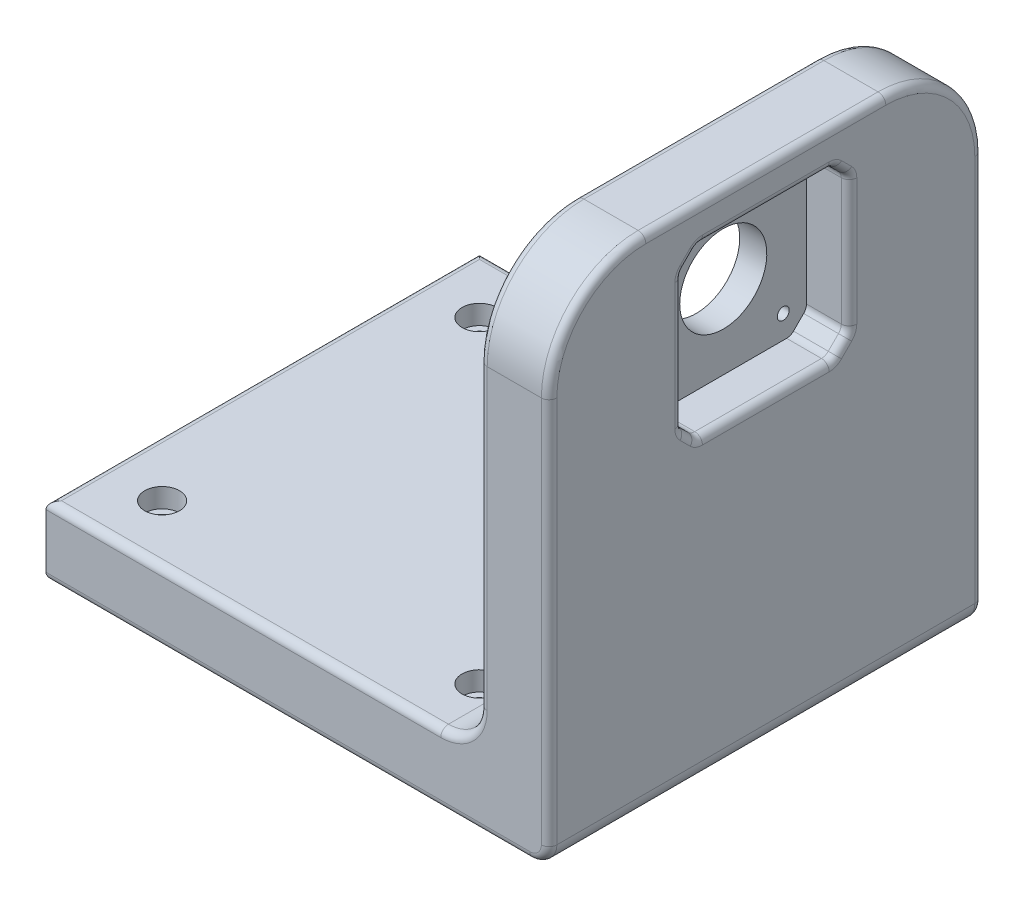
SolidWorks part; units mm, degrees
note: The reader was unsure of these and kept them because the rebuilt part matched: shared geometry of "Sketch9<3>".
ref_plane "Front" through (0, 0, 0) normal (0, 0, 1) x (1, 0, 0)
ref_plane "Top" through (0, 0, 0) normal (0, 1, 0) x (1, 0, 0)
ref_plane "Right" through (0, 0, 0) normal (1, 0, 0) x (0, 0, -1)
sketch "Sketch1" plane through (0, 0, 0) normal (0, 0, 1) x (1, 0, 0)
  line L1 (130, 0) -> (130, 130)
  line L2 (130, 130) -> (112, 130)
  line L3 (112, 130) -> (112, 18)
  line L8 (0, 0) -> (0, 18)
  line L9 (0, 0) -> (130, 0)
  line L10 (112, 18) -> (0, 18)
  point P4 (0, 0)
  dimension "D1" = 112
  dimension "D2" = 18
  dimension "D3" = 18
  dimension "D4" = 112
extrude "Boss-Extrude1" add sketch "Sketch1" along normal mid plane 112
sketch "Sketch2" plane through (130, 0, 0) normal (1, 0, 0) x (0, 0, -1)
  line L0 (-16.3716, 77.65) -> (16.3716, 77.65)
  line L1 (18.1393, 78.3822) -> (20.7678, 81.0107)
  line L2 (21.5, 82.7784) -> (21.5, 115.5216)
  line L3 (20.7678, 117.2893) -> (18.1393, 119.9178)
  line L4 (16.3716, 120.65) -> (-16.3716, 120.65)
  line L5 (-18.1393, 119.9178) -> (-20.7678, 117.2893)
  line L6 (-21.5, 115.5216) -> (-21.5, 82.7784)
  line L7 (-20.7678, 81.0107) -> (-18.1393, 78.3822)
  line L8 (-16.3716, 78.65) -> (16.3716, 78.65)
  line L9 (17.4322, 79.0893) -> (20.0607, 81.7178)
  line L10 (20.5, 82.7784) -> (20.5, 115.5216)
  line L11 (20.0607, 116.5822) -> (17.4322, 119.2107)
  line L12 (16.3716, 119.65) -> (-16.3716, 119.65)
  line L13 (-17.4322, 119.2107) -> (-20.0607, 116.5822)
  line L14 (-20.5, 115.5216) -> (-20.5, 82.7784)
  line L15 (-20.0607, 81.7178) -> (-17.4322, 79.0893)
  line L16 (-16.3716, 78.65) -> (16.3716, 78.65) construction
  line L17 (17.4322, 79.0893) -> (20.0607, 81.7178) construction
  line L18 (20.5, 82.7784) -> (20.5, 115.5216) construction
  line L19 (20.0607, 116.5822) -> (17.4322, 119.2107) construction
  line L20 (16.3716, 119.65) -> (-16.3716, 119.65) construction
  line L21 (-17.4322, 119.2107) -> (-20.0607, 116.5822) construction
  line L22 (-20.5, 115.5216) -> (-20.5, 82.7784) construction
  line L23 (-20.0607, 81.7178) -> (-17.4322, 79.0893) construction
  arc A0 (16.3716, 77.65) -> (18.1393, 78.3822) centre (16.3716, 80.15) ccw
  arc A1 (20.7678, 81.0107) -> (21.5, 82.7784) centre (19, 82.7784) ccw
  arc A2 (21.5, 115.5216) -> (20.7678, 117.2893) centre (19, 115.5216) ccw
  arc A3 (18.1393, 119.9178) -> (16.3716, 120.65) centre (16.3716, 118.15) ccw
  arc A4 (-16.3716, 120.65) -> (-18.1393, 119.9178) centre (-16.3716, 118.15) ccw
  arc A5 (-20.7678, 117.2893) -> (-21.5, 115.5216) centre (-19, 115.5216) ccw
  arc A6 (-21.5, 82.7784) -> (-20.7678, 81.0107) centre (-19, 82.7784) ccw
  arc A7 (-18.1393, 78.3822) -> (-16.3716, 77.65) centre (-16.3716, 80.15) ccw
  arc A8 (16.3716, 78.65) -> (17.4322, 79.0893) centre (16.3716, 80.15) ccw
  arc A9 (20.0607, 81.7178) -> (20.5, 82.7784) centre (19, 82.7784) ccw
  arc A10 (20.5, 115.5216) -> (20.0607, 116.5822) centre (19, 115.5216) ccw
  arc A11 (17.4322, 119.2107) -> (16.3716, 119.65) centre (16.3716, 118.15) ccw
  arc A12 (-16.3716, 119.65) -> (-17.4322, 119.2107) centre (-16.3716, 118.15) ccw
  arc A13 (-20.0607, 116.5822) -> (-20.5, 115.5216) centre (-19, 115.5216) ccw
  arc A14 (-20.5, 82.7784) -> (-20.0607, 81.7178) centre (-19, 82.7784) ccw
  arc A15 (-17.4322, 79.0893) -> (-16.3716, 78.65) centre (-16.3716, 80.15) ccw
  arc A16 (16.3716, 78.65) -> (17.4322, 79.0893) centre (16.3716, 80.15) ccw construction
  arc A17 (20.0607, 81.7178) -> (20.5, 82.7784) centre (19, 82.7784) ccw construction
  arc A18 (20.5, 115.5216) -> (20.0607, 116.5822) centre (19, 115.5216) ccw construction
  arc A19 (17.4322, 119.2107) -> (16.3716, 119.65) centre (16.3716, 118.15) ccw construction
  arc A20 (-16.3716, 119.65) -> (-17.4322, 119.2107) centre (-16.3716, 118.15) ccw construction
  arc A21 (-20.0607, 116.5822) -> (-20.5, 115.5216) centre (-19, 115.5216) ccw construction
  arc A22 (-20.5, 82.7784) -> (-20.0607, 81.7178) centre (-19, 82.7784) ccw construction
  arc A23 (-17.4322, 79.0893) -> (-16.3716, 78.65) centre (-16.3716, 80.15) ccw construction
  dimension "D1" = 0
  dimension "D2" = 1
extrude "Cut-Extrude1" cut sketch "Sketch2" against normal blind 11 contours L23 A23 L16 A16 L17 A17 L18 A18 L19 A19 L20 A20 L21 A21 L22 A22 | L7 A7 L0 A0 L1 A1 L2 A2 L3 A3 L4 A4 L5 A5 L6 A6
sketch "Sketch6" plane through (119, 0, 0) normal (-1, 0, 0) x (0, 0, 1)
  circle A0 centre (0, 99.15) radius 11 construction
  circle A1 centre (0, 99.15) radius 11
  circle A2 centre (0, 99.15) radius 11.25
  dimension "D1" = 0.25
extrude "Cut-Extrude3" cut sketch "Sketch6" along normal up to surface (7 mm away) up to face at (112, 74, 0)
sketch "Sketch7" plane through (112, 0, 0) normal (-1, 0, 0) x (0, 0, 1)
  circle A0 centre (-15.5, 83.65) radius 1.55 construction
  circle A1 centre (15.5, 83.65) radius 1.55 construction
  circle A2 centre (15.5, 114.65) radius 1.55 construction
  circle A3 centre (-15.5, 114.65) radius 1.55 construction
  circle A4 centre (-15.5, 83.65) radius 1.55
  circle A5 centre (15.5, 83.65) radius 1.55
  circle A6 centre (15.5, 114.65) radius 1.55
  circle A7 centre (-15.5, 114.65) radius 1.55
extrude "Cut-Extrude4" cut sketch "Sketch7" against normal up to next
sketch "Sketch8" plane through (112, 0, 0) normal (-1, 0, 0) x (0, 0, 1)
  circle A0 centre (-15.5, 114.65) radius 2.75
  circle A1 centre (-15.5, 114.65) radius 1.55
  circle A2 centre (-15.5, 114.65) radius 1.55
  circle A3 centre (15.5, 114.65) radius 1.55
  circle A4 centre (15.5, 114.65) radius 1.55
  circle A5 centre (15.5, 83.65) radius 1.55
  circle A6 centre (15.5, 83.65) radius 1.55
  circle A7 centre (-15.5, 83.65) radius 1.55
  circle A8 centre (-15.5, 83.65) radius 1.55
  circle A9 centre (15.5, 114.65) radius 2.75
  circle A10 centre (15.5, 83.65) radius 2.75
  circle A11 centre (-15.5, 83.65) radius 2.75
  dimension "D5" = 5.5
  dimension "D1" = 0
  dimension "D2" = 0
  dimension "D3" = 0
  dimension "D4" = 0
extrude "Cut-Extrude5" cut sketch "Sketch8" against normal blind 3
sketch "Sketch9" plane through (0, 18, 0) normal (0, 1, 0) x (1, 0, 0)
  line L0 (112, 56) -> (0, 56) construction
  line L1 (0, -56) -> (0, 56) construction
  line L2 (112, -56) -> (0, -56) construction
  line L3 (112, -56) -> (112, 56) construction
  circle A0 centre (15, 41) radius 4.5
  circle A1 centre (15, -41) radius 4.5
  circle A2 centre (97, 41) radius 4.5
  circle A3 centre (97, -41) radius 4.5
  circle A4 centre (15, 41) radius 2.75
  circle A5 centre (97, 41) radius 2.75
  circle A6 centre (97, -41) radius 2.75
  circle A7 centre (15, -41) radius 2.75
  dimension "D1" = 9
  dimension "D2" = 15
  dimension "D6" = 5.5
  dimension "D3" = 15
  dimension "D4" = 15
  dimension "D5" = 15
extrude "Cut-Extrude6" cut sketch "Sketch9" against normal blind 5 contours A7 | A1 A7 | A0 A4 | A4 | A2 A5 | A5 | A3 A6 | A6
extrude "Cut-Extrude7" cut sketch "Sketch9<3>" against normal through all both and the other way through all contours A4 | A5 | A6 | A7
sketch "Sketch9<3>" plane through (0, 18, 0) normal (0, 1, 0) x (1, 0, 0) same geometry as "Sketch9"
fillet "Fillet1" radius 10 1 edges at (112, 18, 0)
fillet "Fillet2" radius 25 2 edges at (121, 130, -56) (121, 130, 56)
fillet "Fillet3" radius 5 1 edges at (130, 0, 0)
fillet "Fillet4" radius 2 36 edges at (62.5, 0, 56) (128.5355, 1.4645, 56) (130, 55, 56) (130, 122.6777, 48.6777) (62.5, 0, -56) (128.5355, 1.4645, -56) (130, 55, -56) (130, 122.6777, -48.6777) (51, 18, 56) (109.0711, 20.9289, 56) (112, 66.5, 56) (112, 122.6777, 48.6777) (51, 18, -56) (109.0711, 20.9289, -56) (112, 66.5, -56) (112, 122.6777, -48.6777) (130, 130, 0) (112, 130, 0) (0, 0, 0) (0, 18, 0) (130, 120.4597, -17.3283) (130, 118.6036, -19.4536) (130, 116.4783, -21.3097) (130, 99.15, -21.5) (130, 81.8217, -21.3097) (130, 79.6964, -19.4536) (130, 77.8403, -17.3283) (130, 77.65, 0) (130, 77.8403, 17.3283) (130, 79.6964, 19.4536) (130, 81.8217, 21.3097) (130, 99.15, 21.5) (130, 116.4783, 21.3097) (130, 118.6036, 19.4536) (130, 120.4597, 17.3283) (130, 120.65, 0)
